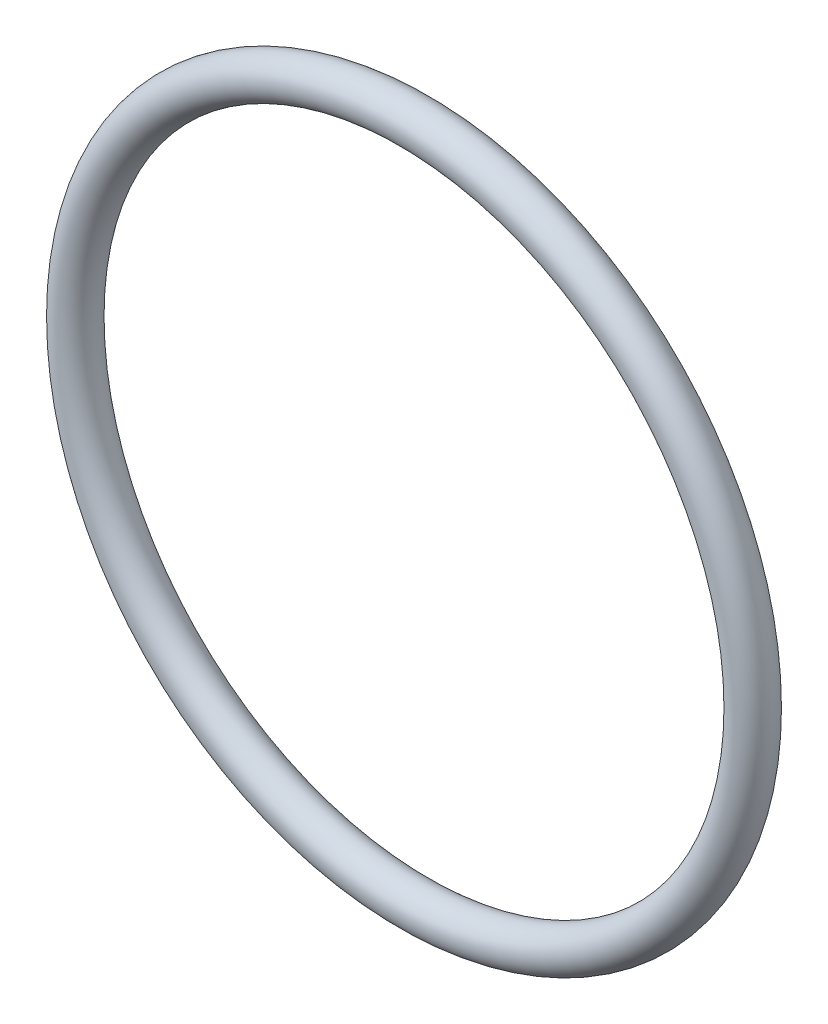
SolidWorks part; units mm, degrees
material "Rubber"
ref_plane "Front" through (0, 0, 0) normal (0, 0, 1) x (1, 0, 0)
ref_plane "Top" through (0, 0, 0) normal (0, 1, 0) x (1, 0, 0)
ref_plane "Right" through (0, 0, 0) normal (1, 0, 0) x (0, 0, -1)
sketch "Sketch1" plane through (0, 0, 0) normal (1, 0, 0) x (0, -1, 0)
  line L0 (0, -1.3081) -> (0, 1.3081) construction
  line L2 (-25.3975, 0) -> (25.3975, 0) construction
  line L3 (-20.4724, 0) -> (20.4724, 0) construction
  circle A0 centre (21.7805, 0) radius 1.3081
  point P9 (20.4724, 0)
  point P10 (23.0886, 0)
  point P13 (21.7805, 1.3081)
  point P14 (21.7805, -1.3081)
  dimension "Width" = 2.6162
  dimension "ID" = 40.9448
revolve "Revolve1" add sketch "Sketch1" angle 360 about L0
ref_axis "Axis1" through (0, 0, 0) along (0, 0, 1)
